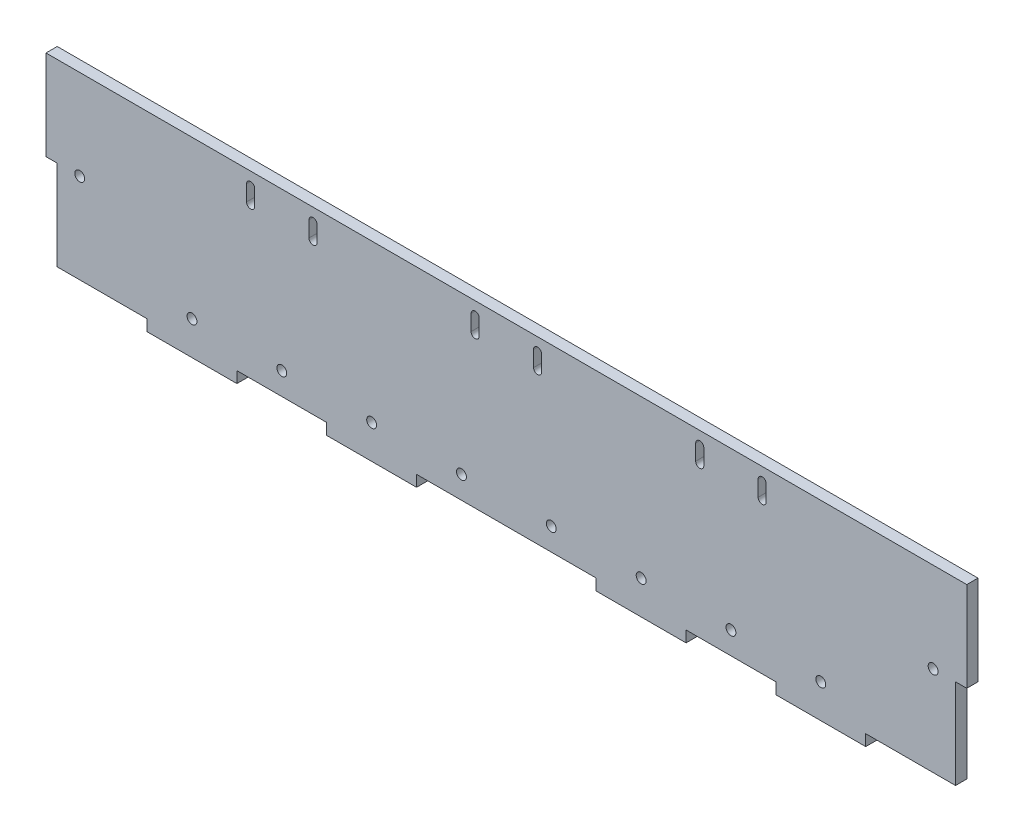
SolidWorks part; units mm, degrees
ref_plane "前视基准面" through (0, 0, 0) normal (0, 0, 1) x (1, 0, 0)
ref_plane "上视基准面" through (0, 0, 0) normal (0, 1, 0) x (1, 0, 0)
ref_plane "右视基准面" through (0, 0, 0) normal (1, 0, 0) x (0, 0, -1)
sketch "草图1" plane through (0, 0, 0) normal (0, 0, 1) x (1, 0, 0)
  line L2 (-200, 150) -> (200, 150)
  line L3 (200, -150) -> (200, -110)
  line L4 (-200, -150) -> (-200, -110)
  line L5 (-200, -150) -> (-160, -150)
  line L6 (-200, -150) -> (-160, -150)
  line L7 (-160, -150) -> (-160, -155)
  line L8 (-160, -155) -> (-120, -155)
  line L9 (-120, -155) -> (-120, -150)
  line L10 (-120, -150) -> (-80, -150)
  line L11 (-80, -150) -> (-80, -155)
  line L12 (-80, -155) -> (-40, -155)
  line L13 (-40, -155) -> (-40, -150)
  line L14 (-40, -150) -> (40, -150)
  line L15 (40, -150) -> (40, -155)
  line L16 (40, -155) -> (80, -155)
  line L17 (80, -155) -> (80, -150)
  line L18 (80, -150) -> (120, -150)
  line L19 (120, -150) -> (120, -155)
  line L20 (120, -155) -> (160, -155)
  line L21 (160, -155) -> (160, -150)
  line L22 (80, -150) -> (120, -150)
  line L23 (-120, -150) -> (-80, -150)
  line L24 (-40, -150) -> (40, -150)
  line L25 (160, -150) -> (200, -150)
  line L26 (-200, 110) -> (-200, 150)
  line L27 (-200, -70) -> (-200, -30)
  line L28 (-205, -30) -> (-205, 30)
  line L29 (-205, 30) -> (-200, 30)
  line L30 (-200, 30) -> (-200, 70)
  line L31 (-200, 70) -> (-205, 70)
  line L32 (-205, 70) -> (-205, 110)
  line L33 (-205, 110) -> (-200, 110)
  line L34 (-205, -30) -> (-200, -30)
  line L35 (-200, -70) -> (-205, -70)
  line L36 (-205, -70) -> (-205, -110)
  line L37 (-205, -110) -> (-200, -110)
  line L38 (-200, 30) -> (-200, 70)
  line L39 (200, 110) -> (200, 150)
  line L40 (205, -70) -> (205, -110)
  line L41 (205, -110) -> (200, -110)
  line L42 (200, -70) -> (205, -70)
  line L43 (205, -30) -> (200, -30)
  line L44 (205, -30) -> (205, 30)
  line L45 (205, 30) -> (200, 30)
  line L46 (200, 70) -> (205, 70)
  line L47 (205, 70) -> (205, 110)
  line L48 (205, 110) -> (200, 110)
  line L49 (200, 30) -> (200, 70)
  line L50 (200, -70) -> (200, -30)
  circle A0 centre (-140, -140) radius 2.2
  circle A1 centre (-100, -140) radius 2.2
  circle A2 centre (-60, -140) radius 2.2
  circle A3 centre (-20, -140) radius 2.2
  circle A4 centre (20, -140) radius 2.2
  circle A5 centre (60, -140) radius 2.2
  circle A6 centre (100, -140) radius 2.2
  circle A7 centre (140, -140) radius 2.2
  circle A8 centre (-190, 110) radius 2.2
  circle A9 centre (-190, 70) radius 2.2
  circle A10 centre (-190, 30) radius 2.2
  circle A11 centre (-190, -30) radius 2.2
  circle A12 centre (-190, -70) radius 2.2
  circle A13 centre (-190, -110) radius 2.2
  circle A14 centre (190, -110) radius 2.2
  circle A15 centre (190, -70) radius 2.2
  circle A16 centre (190, -30) radius 2.2
  circle A17 centre (190, 30) radius 2.2
  circle A18 centre (190, 70) radius 2.2
  circle A19 centre (190, 110) radius 2.2
extrude "凸台-拉伸1" add sketch "草图1" along normal blind 5 contours L42 L50 L43 L44 L45 L49 L46 L47 L48 L39 L2 L26 L33 L32 L31 L30 L29 L28 L34 L27 L35 L36 L37 L4 L5 L7 L8 L9 L10 L11 L12 L13 L14 L15 L16 L17 L18 L19 L20 L21 L25 L3 L41 L40 A18 A16 A14 region at (0, -0.8611, 0)
sketch "草图2" plane through (0, 0, 5) normal (0, 0, 1) x (1, 0, 0)
  line L0 (-205, -70) -> (205, -70)
  line L1 (-205, -70) -> (-205, 156.1054)
  line L2 (205, -70) -> (205, 156.1054)
  line L3 (-205, 156.1054) -> (205, 156.1054)
extrude "切除-拉伸2" cut sketch "草图2" against normal blind 5
sketch "草图4" plane through (0, 0, 5) normal (0, 0, 1) x (1, 0, 0)
  line L0 (-205, -70) -> (205, -70)
  line L1 (-205, -70) -> (-205, -89.4867)
  line L2 (205, -70) -> (205, -89.4867)
  line L3 (-205, -89.4867) -> (205, -89.4867)
extrude "凸台-拉伸3" add sketch "草图4" against normal blind 5
sketch "草图5" plane through (0, 0, 0) normal (0, 0, -1) x (-1, 0, 0)
  line L5 (86.1, -75.8) -> (86.1, -82.8) construction
  line L8 (87.9081, -75.8) -> (87.9081, -82.8)
  line L12 (13.9, -75.8) -> (13.9, -82.8) construction
  line L15 (12.0919, -75.8) -> (12.0919, -82.8)
  line L18 (-13.9, -75.8) -> (-13.9, -82.8) construction
  line L19 (-12.0919, -75.8) -> (-12.0919, -82.8)
  line L20 (-15.7081, -75.8) -> (-15.7081, -82.8)
  line L21 (15.7081, -75.8) -> (15.7081, -82.8)
  line L22 (84.2919, -75.8) -> (84.2919, -82.8)
  line L23 (113.9, -75.8) -> (113.9, -82.8) construction
  line L24 (112.0919, -75.8) -> (112.0919, -82.8)
  line L25 (115.7081, -75.8) -> (115.7081, -82.8)
  line L26 (-86.1, -75.8) -> (-86.1, -82.8) construction
  line L27 (-87.9081, -75.8) -> (-87.9081, -82.8)
  line L28 (-84.2919, -75.8) -> (-84.2919, -82.8)
  line L29 (-113.9, -75.8) -> (-113.9, -82.8) construction
  line L30 (-112.0919, -75.8) -> (-112.0919, -82.8)
  line L31 (-115.7081, -75.8) -> (-115.7081, -82.8)
  arc A12 (-12.0919, -75.8) -> (-15.7081, -75.8) centre (-13.9, -75.8) ccw
  arc A13 (-15.7081, -82.8) -> (-12.0919, -82.8) centre (-13.9, -82.8) ccw
  arc A14 (12.0919, -75.8) -> (15.7081, -75.8) centre (13.9, -75.8) cw
  arc A15 (15.7081, -82.8) -> (12.0919, -82.8) centre (13.9, -82.8) cw
  arc A16 (87.9081, -75.8) -> (84.2919, -75.8) centre (86.1, -75.8) ccw
  arc A17 (84.2919, -82.8) -> (87.9081, -82.8) centre (86.1, -82.8) ccw
  arc A18 (112.0919, -75.8) -> (115.7081, -75.8) centre (113.9, -75.8) cw
  arc A19 (115.7081, -82.8) -> (112.0919, -82.8) centre (113.9, -82.8) cw
  arc A20 (-87.9081, -75.8) -> (-84.2919, -75.8) centre (-86.1, -75.8) cw
  arc A21 (-84.2919, -82.8) -> (-87.9081, -82.8) centre (-86.1, -82.8) cw
  arc A22 (-112.0919, -75.8) -> (-115.7081, -75.8) centre (-113.9, -75.8) ccw
  arc A23 (-115.7081, -82.8) -> (-112.0919, -82.8) centre (-113.9, -82.8) ccw
  point P6 (-13.9, -79.3)
  point P15 (13.9, -79.3)
  point P20 (86.1, -79.3)
  point P29 (113.9, -79.3)
  point P34 (-86.1, -79.3)
  point P41 (-113.9, -79.3)
extrude "切除-拉伸3" cut sketch "草图5" against normal blind 10
